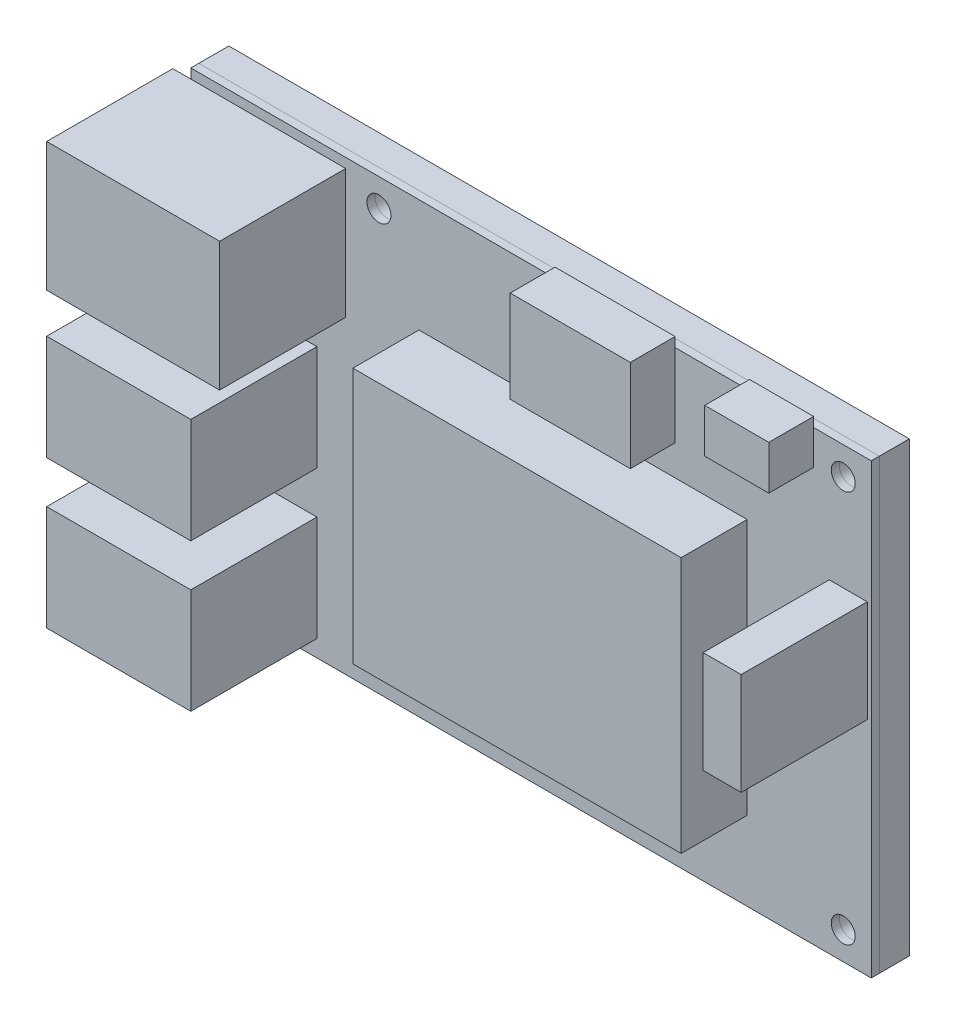
SolidWorks part; units mm, degrees
ref_plane "Front Plane" through (0, 0, 0) normal (0, 0, 1) x (1, 0, 0)
ref_plane "Top Plane" through (0, 0, 0) normal (0, 1, 0) x (1, 0, 0)
ref_plane "Right Plane" through (0, 0, 0) normal (1, 0, 0) x (0, 0, -1)
sketch "Sketch1" plane through (0, 0, 0) normal (0, 0, 1) x (1, 0, 0)
  line L0 (-19, 24.5) -> (39, 24.5) construction
  line L1 (-42.5, 27.975) -> (42.5, 27.975)
  line L2 (-42.5, 27.975) -> (-42.5, -27.975)
  line L3 (-42.5, -27.975) -> (42.5, -27.975)
  line L4 (42.5, 27.975) -> (42.5, -27.975)
  line L5 (39, 24.5) -> (39, -24.5) construction
  line L6 (39, -24.5) -> (-19, -24.5) construction
  line L7 (-19, -24.5) -> (-19, 24.5) construction
  line L8 (39, 0) -> (42.5, 0) construction
  line L9 (55, 0) -> (-55, 0) construction
  line L10 (0, -55) -> (0, 55) construction
  circle A0 centre (-19, 24.5) radius 1.5
  circle A1 centre (-19, -24.5) radius 1.5
  circle A2 centre (39, 24.5) radius 1.5
  circle A3 centre (39, -24.5) radius 1.5
  point P12 (-19, 0)
  point P17 (0, 27.975)
  dimension "D1" = 3
  dimension "D2" = 58
  dimension "D3" = 49
  dimension "D4" = 55.95
  dimension "D5" = 85
  dimension "D6" = 3.5
extrude "Boss-Extrude1" add sketch "Sketch1" along normal blind 1
extrude "Boss-Extrude2-lower-keepout" add sketch "Sketch1<2>" against normal blind 3.75 separate body
sketch "Sketch1<2>" plane through (0, 0, 0) normal (0, 0, 1) x (1, 0, 0) same geometry as "Sketch1"
sketch "Sketch3" plane through (0, 0, 1) normal (0, 0, 1) x (1, 0, 0)
  line L0 (42.5, 27.975) -> (42.5, -27.975) construction
  line L1 (-14, 13.875) -> (27, 13.875)
  line L2 (-14, 13.875) -> (-14, -18.125)
  line L3 (-14, -18.125) -> (27, -18.125)
  line L4 (27, 13.875) -> (27, -18.125)
  line L5 (-42.5, 27.975) -> (42.5, 27.975) construction
  dimension "D1" = 41
  dimension "D2" = 32
  dimension "D3" = 15.5
  dimension "D4" = 14.1
extrude "Boss-Extrude3" add sketch "Sketch3" along normal blind 8.25
sketch "Sketch4" plane through (0, 0, 1) normal (0, 0, 1) x (1, 0, 0)
  line L0 (-44.7495, -0.865) -> (-34.7495, -0.865) construction
  line L1 (-44.7495, 5.705) -> (-26.7495, 5.705)
  line L2 (-44.7495, 5.705) -> (-44.7495, -7.435)
  line L3 (-44.7495, -7.435) -> (-26.7495, -7.435)
  line L4 (-26.7495, 5.705) -> (-26.7495, -7.435)
  line L5 (-44.7495, -12.735) -> (-26.7495, -12.735)
  line L6 (-44.7495, -12.735) -> (-44.7495, -25.875)
  line L7 (-44.7495, -25.875) -> (-26.7495, -25.875)
  line L8 (-26.7495, -12.735) -> (-26.7495, -25.875)
  line L9 (-44.7495, -19.305) -> (-34.7495, -19.305) construction
  line L10 (42.5, -27.975) -> (42.5, 27.975) construction
  line L11 (37.245, 12.475) -> (42, 12.475)
  line L12 (-44.7495, 26.775) -> (-23.1495, 26.775)
  line L13 (-44.7495, 26.775) -> (-44.7495, 10.675)
  line L14 (-44.7495, 10.675) -> (-23.1495, 10.675)
  line L15 (-23.1495, 26.775) -> (-23.1495, 10.675)
  line L16 (37.245, 12.475) -> (37.245, -0.275)
  line L17 (37.245, -0.275) -> (42, -0.275)
  line L18 (42, 12.475) -> (42, -0.275)
  line L19 (42.5, 27.975) -> (-42.5, 27.975) construction
  dimension "D1" = 18
  dimension "D2" = 13.14
  dimension "D3" = 10
  dimension "D4" = 5.3
  dimension "D5" = 2.1
  dimension "D6" = 21.6
  dimension "D7" = 1.2
  dimension "D8" = 16.1
  dimension "D9" = 4.755
  dimension "D10" = 12.75
  dimension "D11" = 0.5
  dimension "D12" = 15.5
extrude "Boss-Extrude4" add sketch "Sketch4" along normal blind 15.75
sketch "Sketch5" plane through (0, 0, 1) normal (0, 0, 1) x (1, 0, 0)
  line L1 (3, 29.175) -> (18, 29.175)
  line L2 (3, 29.175) -> (3, 17.675)
  line L3 (3, 17.675) -> (18, 17.675)
  line L4 (18, 29.175) -> (18, 17.675)
  line L5 (27.3, 29.175) -> (35.3, 29.175)
  line L6 (27.3, 29.175) -> (27.3, 23.675)
  line L7 (27.3, 23.675) -> (35.3, 23.675)
  line L8 (35.3, 29.175) -> (35.3, 23.675)
  dimension "D1" = 15
  dimension "D2" = 8
  dimension "D3" = 11.5
  dimension "D4" = 5.5
  dimension "D5" = 1.2
  dimension "D6" = 24.5
  dimension "D7" = 7.2
extrude "Boss-Extrude5" add sketch "Sketch5" along normal blind 5.6
sketch "Sketch6" plane through (0, 0, 0) normal (0, 0, 1) x (1, 0, 0)
  line L0 (-42.5, -27.975) -> (42.5, -27.975) construction
  line L1 (-0.5969, -28.475) -> (-12.2069, -28.475)
  line L2 (-0.5969, -28.475) -> (-0.5969, -12.725)
  line L3 (-0.5969, -12.725) -> (-12.2069, -12.725)
  line L4 (-12.2069, -28.475) -> (-12.2069, -12.725)
  dimension "D1" = 11.61
  dimension "D2" = 15.75
  dimension "D3" = 0.5
extrude "Boss-Extrude6" add sketch "Sketch6" against normal blind 4 separate body
sketch "Sketch7" plane through (-44.7495, 0, 0) normal (-1, 0, 0) x (0, 0, 1)
  line L0 (1, -12.735) -> (1, -25.875) construction
  line L1 (7.7, -14.155) -> (2.7, -14.155)
  line L2 (7.7, -14.155) -> (7.7, -24.4596)
  line L3 (7.7, -24.4596) -> (2.7, -24.4596)
  line L4 (2.7, -14.155) -> (2.7, -24.4596)
  line L5 (16.75, -25.875) -> (1, -25.875) construction
  line L6 (16.75, -12.735) -> (1, -12.735) construction
  point P10 (8.875, -12.735)
  dimension "D1" = 1.7
  dimension "D2" = 1.4154
  dimension "D3" = 1.42
  dimension "D4" = 5
extrude "Cut-Extrude1" cut sketch "Sketch7" against normal blind 12
ref_plane "Plane1" through (0, 0, 8.875) normal (0, 0, 1) x (1, 0, 0)
mirror "Mirror1" about plane through (0, 0, 8.875) normal (0, 0, 1) of "Cut-Extrude1"
ref_plane "Plane2" through (0, -10.085, 0) normal (0, 1, 0) x (1, 0, 0)
mirror "Mirror2" about plane through (0, -10.085, 0) normal (0, 1, 0) of "Mirror1"
